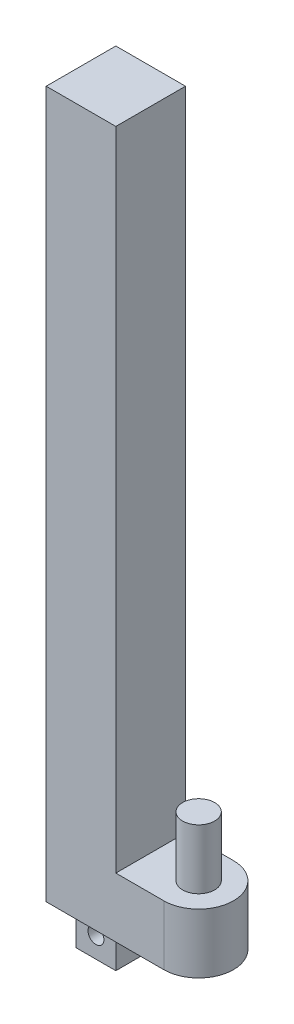
SolidWorks part; units mm, degrees
ref_plane "Front Plane" through (0, 0, 0) normal (0, 0, 1) x (1, 0, 0)
ref_plane "Top Plane" through (0, 0, 0) normal (0, 1, 0) x (1, 0, 0)
ref_plane "Right Plane" through (0, 0, 0) normal (1, 0, 0) x (0, 0, -1)
sketch "Sketch1" plane through (0, 0, 0) normal (0, 1, 0) x (1, 0, 0)
  line L0 (17.5, 17.5) -> (41.6263, 17.5)
  line L1 (-17.5, -17.5) -> (17.5, -17.5)
  line L2 (-17.5, -17.5) -> (-17.5, 17.5)
  line L3 (-17.5, 17.5) -> (17.5, 17.5)
  line L4 (17.5, -17.5) -> (17.5, 17.5)
  line L5 (-17.5, -17.5) -> (17.5, 17.5) construction
  line L6 (-17.5, 17.5) -> (17.5, -17.5) construction
  line L7 (17.5, -17.5) -> (41.6263, -17.5)
  arc A0 (41.6263, 17.5) -> (41.6263, -17.5) centre (41.6263, 0) cw
  circle A1 centre (41.6263, 0) radius 8.0576
  point P0 (0, 0)
  dimension "D1" = 35
  dimension "D2" = 35
extrude "Boss-Extrude1" add sketch "Sketch1" along normal blind 355 contours L1 L4 L3 L2 region at (0, 0, 0)
extrude "Boss-Extrude2" add sketch "Sketch1<3>" along normal blind 30 contours A0 L0 L4 L7 A1 region at (29.5631, 0, -16.9561)
sketch "Sketch1<3>" plane through (0, 0, 0) normal (0, 1, 0) x (1, 0, 0) same geometry as "Sketch1"
extrude "Boss-Extrude3" add sketch "Sketch1<4>" along normal blind 60 contours A1 region at (41.6263, 0, 0)
sketch "Sketch1<4>" plane through (0, 0, 0) normal (0, 1, 0) x (1, 0, 0) same geometry as "Sketch1"
sketch "Sketch2" plane through (0, 0, 0) normal (0, -1, 0) x (1, 0, 0)
  line L1 (-10, 10) -> (10, 10)
  line L2 (-10, 10) -> (-10, -10)
  line L3 (-10, -10) -> (10, -10)
  line L4 (10, 10) -> (10, -10)
  line L5 (-10, 10) -> (10, -10) construction
  line L6 (-10, -10) -> (10, 10) construction
  point P0 (0, 0)
  dimension "D1" = 20
  dimension "D2" = 20
extrude "Boss-Extrude4" add sketch "Sketch2" along normal blind 20
sketch "Sketch3" plane through (0, 0, 10) normal (0, 0, 1) x (1, 0, 0)
  line L0 (-10, -3.8543) -> (10, -3.8543) construction
  line L1 (-10, -20) -> (-10, 0) construction
  line L2 (10, -20) -> (10, 0) construction
  line L3 (10, -3.8543) -> (-10, -15.3122) construction
  line L4 (-10, -15.3122) -> (10, -15.3122) construction
  circle A0 centre (0, -9.5832) radius 4
  dimension "D1" = 8
extrude "Cut-Extrude1" cut sketch "Sketch3" against normal up to next
